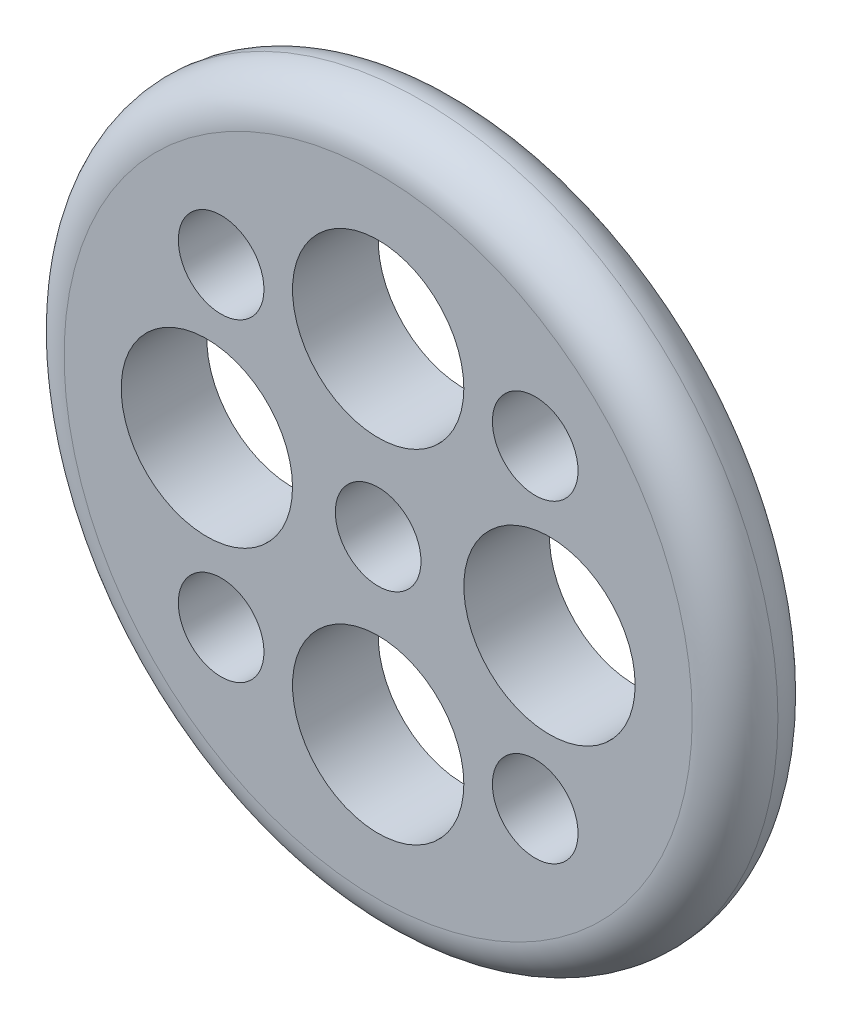
SolidWorks part; units mm, degrees
ref_plane "Front Plane" through (0, 0, 0) normal (0, 0, 1) x (1, 0, 0)
ref_plane "Top Plane" through (0, 0, 0) normal (0, 1, 0) x (1, 0, 0)
ref_plane "Right Plane" through (0, 0, 0) normal (1, 0, 0) x (0, 0, -1)
sketch "Sketch1" plane through (0, 0, 0) normal (0, 0, 1) x (1, 0, 0)
  circle A0 centre (0, 0) radius 125
  dimension "D1" = 250
extrude "Boss-Extrude1" add sketch "Sketch1" along normal blind 30
fillet "Fillet1" radius 15 2 edges at (125, 0, 0) (125, 0, 30)
sketch "Sketch2" plane through (0, 0, 30) normal (0, 0, 1) x (1, 0, 0)
  circle A0 centre (0, 0) radius 15
  dimension "D1" = 30
extrude "Cut-Extrude1" cut sketch "Sketch2" against normal blind 30
sketch "Sketch3" plane through (0, 0, 30) normal (0, 0, 1) x (1, 0, 0)
  circle A2 centre (0, 60) radius 30
  circle A3 centre (-60, 0) radius 30
  circle A4 centre (0, -60) radius 30
  circle A5 centre (60, 0) radius 30
  circle A6 centre (55, -55) radius 15
  circle A7 centre (-55, -55) radius 15
  circle A8 centre (-55, 55) radius 15
  circle A9 centre (55, 55) radius 15
  circle A10 centre (0, 0) radius 15 construction
  dimension "D1" = 60
  dimension "D2" = 30
  dimension "D3" = 60
  dimension "D4" = 30
  dimension "D5" = 60
  dimension "D6" = 30
  dimension "D7" = 60
  dimension "D8" = 30
  dimension "D9" = 55
  dimension "D10" = 60
  dimension "D11" = 60
  dimension "D12" = 55
extrude "Cut-Extrude2" cut sketch "Sketch3" against normal blind 50
